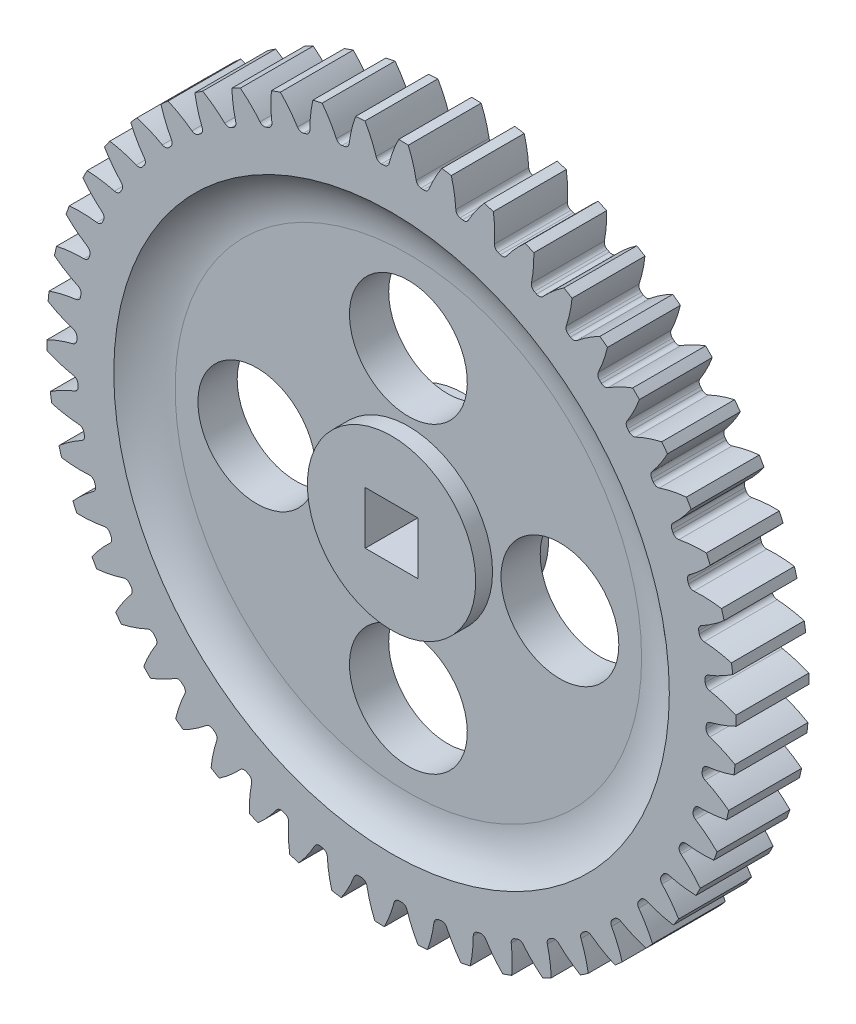
SolidWorks part; units mm, degrees
material "ABS"
ref_plane "Front" through (0, 0, 0) normal (0, 0, 1) x (1, 0, 0)
ref_plane "Top" through (0, 0, 0) normal (0, 1, 0) x (1, 0, 0)
ref_plane "Right" through (0, 0, 0) normal (1, 0, 0) x (0, 0, -1)
sketch "Sketch3" plane through (0, 0, 0) normal (0, 0, 1) x (1, 0, 0)
  circle A0 centre (0, 0) radius 26
  dimension "od" = 52
extrude "gearBody" add sketch "Sketch3" along normal blind 5.5
sketch "Sketch2" plane through (0, 0, 0) normal (0, 0, 1) x (1, 0, 0)
  line L0 (0, 0) -> (21.7041, 8.9901) construction
  line L1 (29.3392, -5.6152) -> (0, 0) construction
  line L2 (0, 0) -> (36.3143, 0) construction
  line L3 (24.9999, -0.0564) -> (24.9435, -1.6792) construction
  line L5 (24.9717, -0.8678) -> (0, 0) construction
  line L7 (0, 0) -> (23.4923, 0) construction
  arc A0 (23.4876, -0.4715) -> (23.4636, -1.1602) centre (0, 0) ccw construction
  arc A1 (25.9973, 0.3721) -> (25.9088, -2.1759) centre (0, 0) ccw construction
  arc A2 (24.9999, -0.0564) -> (24.9435, -1.6792) centre (0, 0) ccw construction
  arc A3 (23.7314, -0.9194) -> (23.738, -0.7303) centre (0, 0) ccw
  arc A4 (29.3392, -5.6152) -> (24.0111, -1.3208) centre (21.0276, -10.4751) ccw
  arc A5 (29.3392, -5.6152) -> (29.6583, 3.5649) centre (0, 0) ccw
  arc A6 (29.6583, 3.5649) -> (24.0448, -0.3492) centre (21.7041, 8.9901) cw
  arc A7 (23.738, -0.7303) -> (24.0448, -0.3492) centre (24.1435, -0.7428) cw
  arc A8 (24.0111, -1.3208) -> (23.7314, -0.9194) centre (24.1368, -0.9351) cw
  point P6 (29.6583, 3.5649)
  point P22 (29.3392, -5.6152)
  dimension "baseDia" = 46.9846
  dimension "od" = 52
  dimension "pd" = 50
  dimension "rd" = 47.4984
  dimension "rFillet" = 0.4057
  dimension "pointX" = 29.6583
  dimension "pointY" = 3.5649
  dimension "CTT" = 1.6228
  dimension "flankCenterAngle" = 22.5
extrude "toothCut" cut sketch "Sketch2" along normal through all
pattern_circular "CirPattern1" count 50 over 360 about axis through (0, 0, 5.5) along (0, 0, -1) of "toothCut"
ref_axis "toothSpace" through (0, 0, 0) along (0.9994, -0.0347, 0)
ref_axis "Axis2" through (25.8763, -2.5328, 0) along (-0.9952, 0.0974, 0)
sketch "boreDia" plane through (0, 0, 0) normal (0, 0, 1) x (1, 0, 0)
  circle A0 centre (0, 0) radius 1.5875
  dimension "boreDia" = 3.175
extrude "bore" cut sketch "boreDia" against normal mid plane 25400
sketch "centerLine" plane through (0, 0, 0) normal (0, 1, 0) x (1, 0, 0)
  line L0 (0, 36.4807) -> (0, -59.6309) construction
ref_plane "CB1plane" through (0, 0, 0) normal (0, 0, -1) x (-1, 0, 0)
ref_plane "CB2plane" through (0, 0, 5.5) normal (0, 0, 1) x (1, 0, 0)
ref_axis "Axis1" through (0, 0, 50) along (0, 0, -1)
sketch "Sketch4" plane through (0, 0, 5.5) normal (0, 0, 1) x (1, 0, 0)
  circle A0 centre (0, 0) radius 20.955
  circle A1 centre (0, 0) radius 6.35
  dimension "D1" = 41.91
  dimension "D2" = 12.7
extrude "Cut-Extrude1" cut sketch "Sketch4" against normal blind 1.27
sketch "Sketch5" plane through (0, 0, 0) normal (0, 0, -1) x (-1, 0, 0)
  circle A0 centre (0, 0) radius 6.35
  circle A1 centre (0, 0) radius 20.955
  dimension "D1" = 12.7
  dimension "D2" = 41.91
extrude "Cut-Extrude2" cut sketch "Sketch5" against normal blind 1.27
fillet "Fillet2" radius 5.08 2 edges at (-20.955, 0, 1.27) (20.955, 0, 4.23)
sketch "Sketch6" plane through (0, 0, 4.23) normal (0, 0, 1) x (1, 0, 0)
  circle A0 centre (11.43, 0) radius 4.445
  dimension "D1" = 8.89
  dimension "D2" = 11.43
extrude "Cut-Extrude3" cut sketch "Sketch6" against normal through all
pattern_circular "CirPattern2" count 4 every 90 about axis through (0, 0, -12700) along (0, 0, 1) of "Cut-Extrude3"
sketch "Sketch7" plane through (0, 0, 5.5) normal (0, 0, 1) x (1, 0, 0)
  circle A0 centre (0, 0) radius 3.175
  dimension "D1" = 6.35
extrude "Cut-Extrude4" [suppressed] cut sketch "Sketch7" against normal up to next
sketch "Sketch8" plane through (0, 0, 0) normal (0, 0, 1) x (1, 0, 0)
  line L1 (-1.985, 1.985) -> (1.985, 1.985)
  line L2 (-1.985, 1.985) -> (-1.985, -1.985)
  line L3 (-1.985, -1.985) -> (1.985, -1.985)
  line L4 (1.985, 1.985) -> (1.985, -1.985)
  line L5 (-1.985, 1.985) -> (1.985, -1.985) construction
  line L6 (-1.985, -1.985) -> (1.985, 1.985) construction
  point P0 (0, 0)
  dimension "D1" = 3.97
  dimension "D2" = 3.97
extrude "Cut-Extrude7" cut sketch "Sketch8" along normal through all
